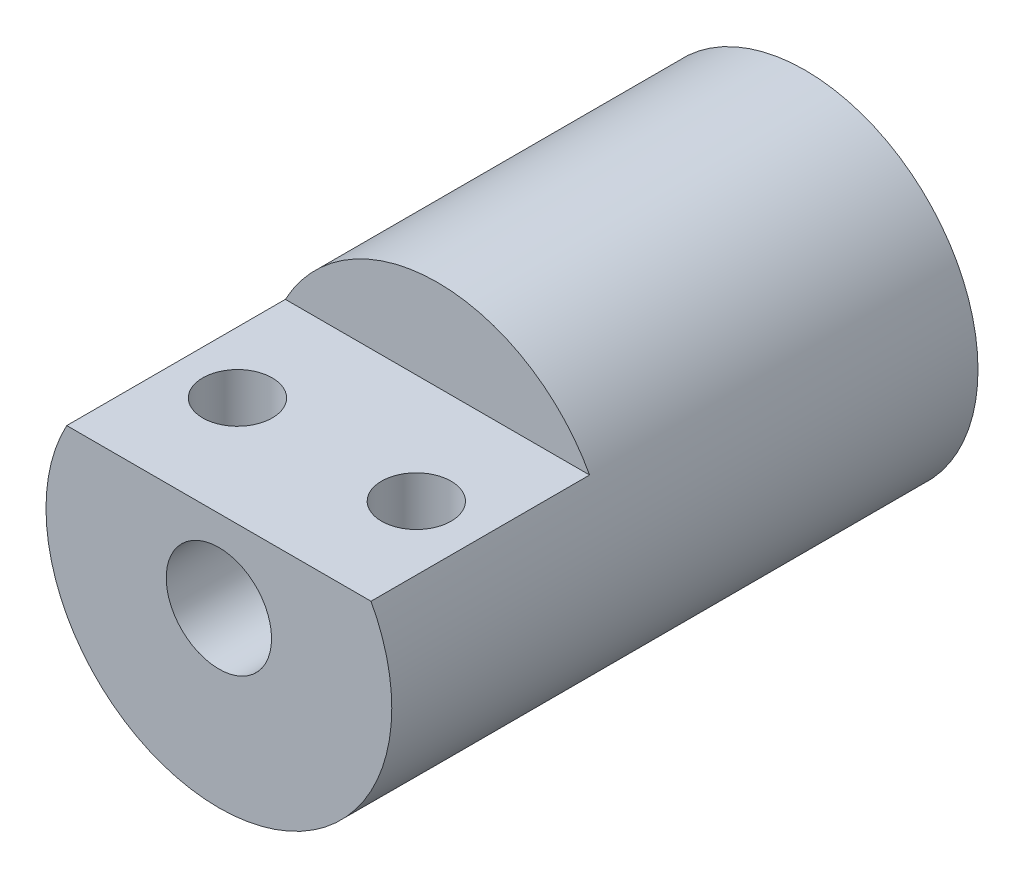
SolidWorks part; units mm, degrees
ref_plane "Front Plane" through (0, 0, 0) normal (0, 0, 1) x (1, 0, 0)
ref_plane "Top Plane" through (0, 0, 0) normal (0, 1, 0) x (1, 0, 0)
ref_plane "Right Plane" through (0, 0, 0) normal (1, 0, 0) x (0, 0, -1)
sketch "Sketch1" plane through (0, 0, 0) normal (0, 0, 1) x (1, 0, 0)
  circle A0 centre (0, 0) radius 8.7
  dimension "D1" = 17.4
extrude "Boss-Extrude1" add sketch "Sketch1" along normal blind 29.5 contours A0
sketch "Sketch2" plane through (0, 0, 29.5) normal (0, 0, 1) x (1, 0, 0)
  line L1 (-7.6555, 8.7) -> (9.3445, 8.7)
  line L2 (-7.6555, 8.7) -> (-7.6555, 4.1331)
  line L3 (-7.6555, 4.1331) -> (9.3445, 4.1331)
  line L4 (9.3445, 8.7) -> (9.3445, 4.1331)
  circle A0 centre (0, 0) radius 8.7 construction
  dimension "D1" = 17
sketch "Sketch4" plane through (0, 0, 0) normal (0, 0, -1) x (-1, 0, 0)
  circle A0 centre (0, 6) radius 1.25
  circle A1 centre (6, 0) radius 1.25
  circle A2 centre (0, -6) radius 1.25
  circle A3 centre (-6, 0) radius 1.25
  dimension "D1" = 2.5
  dimension "D2" = 6
  dimension "D3" = 6
  dimension "D4" = 6
  dimension "D5" = 6
sketch "Sketch5" plane through (0, 0, 0) normal (0, 0, -1) x (-1, 0, 0)
  circle A0 centre (0, 0) radius 1.75
  dimension "D1" = 3.5
extrude "Cut-Extrude1" cut sketch "Sketch5" against normal through all
extrude "Cut-Extrude2" cut sketch "Sketch4" against normal blind 7
sketch "Sketch6" plane through (0, 0, 29.5) normal (0, 0, 1) x (1, 0, 0)
  circle A0 centre (0, 0) radius 2.65
  dimension "D1" = 5.3
extrude "Cut-Extrude3" cut sketch "Sketch6" against normal blind 20.9
extrude "Cut-Extrude4" cut sketch "Sketch2" against normal blind 11 contours L1 L4 L3 L2
fillet "Fillet1" radius 0.3 1 edges at (1.75, 0, 8.6)
sketch "Sketch7" plane through (0, 4.1331, 0) normal (0, 1, 0) x (1, 0, 0)
  circle A0 centre (-4.5645, -24) radius 1.75
  circle A1 centre (4.4355, -24) radius 1.75
  dimension "D1" = 3.5
  dimension "D2" = 3.5
extrude "Cut-Extrude5" cut sketch "Sketch7" against normal through all
